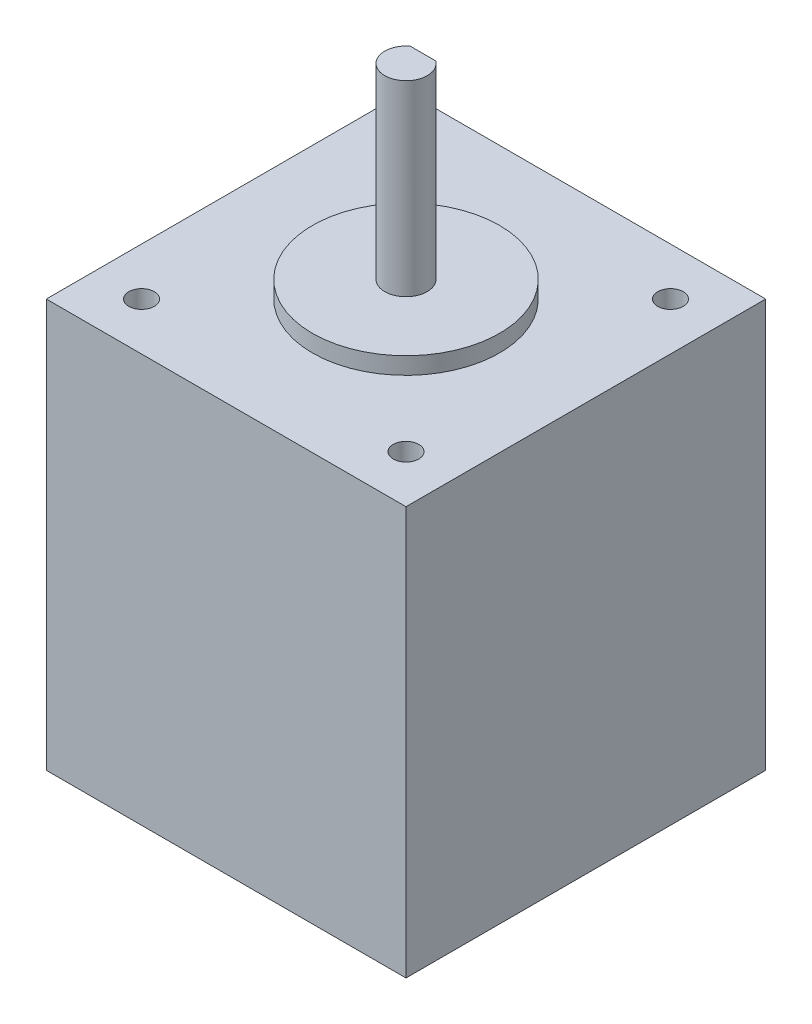
SolidWorks part; units mm, degrees
material "Verzinkter Stahl"
ref_plane "Ebene vorne" through (0, 0, 0) normal (0, 0, 1) x (1, 0, 0)
ref_plane "Ebene oben" through (0, 0, 0) normal (0, 1, 0) x (1, 0, 0)
ref_plane "Ebene rechts" through (0, 0, 0) normal (1, 0, 0) x (0, 0, -1)
sketch "Skizze1" plane through (0, 25, 0) normal (0, -1, 0) x (1, 0, 0)
  line L0 (-21, 64.6) -> (21, 64.6) construction
  line L1 (-21.15, 64.6) -> (21.15, 64.6)
  line L2 (-21.15, 64.6) -> (-21.15, 22.3)
  line L3 (-21.15, 22.3) -> (21.15, 22.3)
  line L4 (21.15, 64.6) -> (21.15, 22.3)
  line L5 (-21.15, 64.6) -> (21.15, 22.3) construction
  line L6 (-21.15, 22.3) -> (21.15, 64.6) construction
  line L7 (15.5, 58.95) -> (15.5, 27.95) construction
  point P0 (0, 43.45)
  point P7 (0, 64.6)
  point P12 (15.5, 43.45)
  dimension "D1" = 42.3
extrude "Aufsatz-Linear austragen1" add sketch "Skizze1" along normal blind 48
sketch "Skizze2" plane through (0, 25, 0) normal (0, 1, 0) x (1, 0, 0)
  circle A0 centre (0, -43.45) radius 11
  dimension "D1" = 22
extrude "Aufsatz-Linear austragen2" add sketch "Skizze2" along normal blind 2
sketch "Skizze3" plane through (0, 27, 0) normal (0, 1, 0) x (1, 0, 0)
  circle A0 centre (0, -43.45) radius 2.5
  dimension "D1" = 5
extrude "Aufsatz-Linear austragen3" add sketch "Skizze3" along normal blind 22
sketch "Skizze4" plane through (0, 49, 0) normal (0, 1, 0) x (1, 0, 0)
  line L1 (-2.5, -40.95) -> (2.5, -40.95)
  line L2 (-2.5, -40.95) -> (-2.5, -41.45)
  line L3 (-2.5, -41.45) -> (2.5, -41.45)
  line L4 (2.5, -40.95) -> (2.5, -41.45)
  line L5 (-2.5, -40.95) -> (2.5, -41.45) construction
  line L6 (-2.5, -41.45) -> (2.5, -40.95) construction
  circle A2 centre (0, -43.45) radius 2.5 construction
  circle A3 centre (0, -43.45) radius 2.5 construction
  point P0 (0, -41.2)
  dimension "D1" = 0.5
extrude "Schnitt-Linear austragen1" cut sketch "Skizze4" against normal blind 15
sketch "Skizze5" plane through (0, 49, 0) normal (0, 1, 0) x (1, 0, 0)
  point P0 (0, -43.45)
ref_axis "Achse1" through (0, 25, 64.6) along (0, 0, -1)
ref_axis "Achse2" through (-21.15, 25, 43.45) along (1, 0, 0)
sketch "Skizze6" plane through (0, 25, 0) normal (0, 1, 0) x (1, 0, 0)
  line L1 (0, -64.6) -> (0, -22.3) construction
  line L2 (-21.15, -43.45) -> (21.15, -43.45) construction
  circle A0 centre (-15.55, -27.9) radius 1.5
  circle A3 centre (-15.55, -59) radius 1.5
  dimension "D4" = 3
  dimension "D1" = 15.55
  dimension "D2" = 31.1
  dimension "D3" = 15.55
extrude "Schnitt-Linear austragen2" cut sketch "Skizze6" against normal blind 4.5
ref_plane "Ebene1" through (0, 0, 0) normal (-1, 0, 0) x (0, 0, 1)
mirror "Spiegeln1" about plane through (0, 0, 0) normal (-1, 0, 0) of "Schnitt-Linear austragen2"
